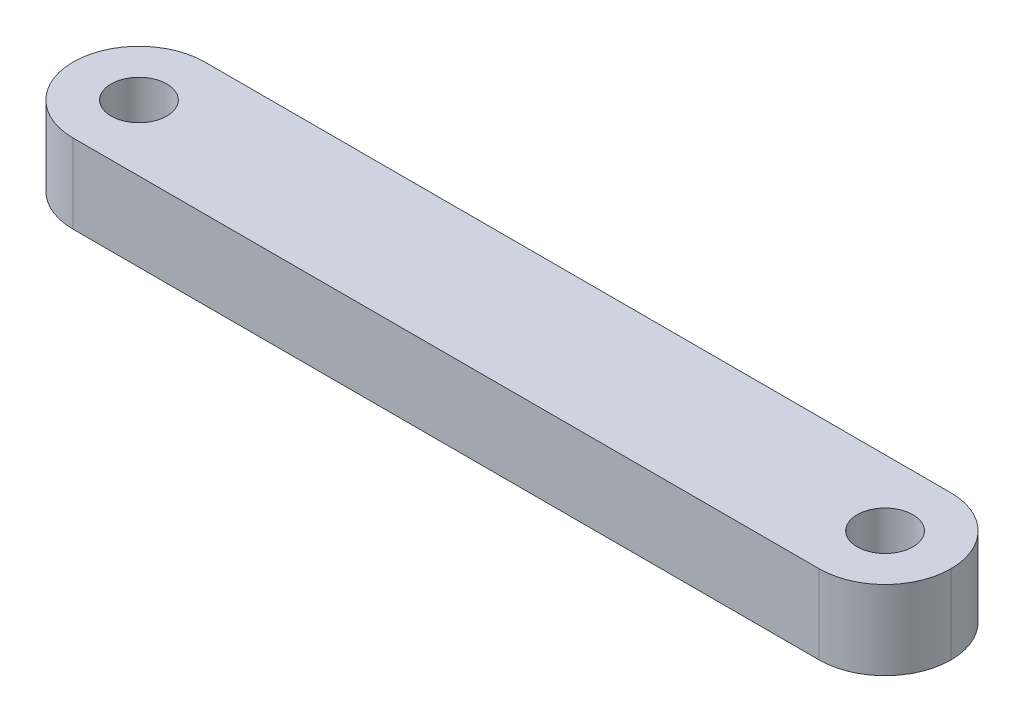
SolidWorks part; units mm, degrees
material "Custom Plastic"
ref_plane "Front Plane" through (0, 0, 0) normal (0, 0, 1) x (1, 0, 0)
ref_plane "Top Plane" through (0, 0, 0) normal (0, 1, 0) x (1, 0, 0)
ref_plane "Right Plane" through (0, 0, 0) normal (1, 0, 0) x (0, 0, -1)
sketch "Sketch1" plane through (0, 0, 0) normal (0, 1, 0) x (1, 0, 0)
  line L0 (-50, -7.5) -> (-42.5, -7.5)
  line L9 (-50, -7.5) -> (50, -7.5)
  line L10 (-50, -7.5) -> (-50, 7.5)
  line L11 (-50, 7.5) -> (50, 7.5)
  line L12 (50, -7.5) -> (50, 7.5)
  line L17 (-50, -7.5) -> (50, 7.5) construction
  line L18 (-50, 7.5) -> (50, -7.5) construction
  line L20 (-42.5, -7.5) -> (-42.5, 7.5)
  line L22 (50, -7.5) -> (42.5, -7.5)
  line L23 (42.5, -7.5) -> (42.5, 7.5)
  circle A0 centre (-42.5, 0) radius 3.175
  circle A1 centre (42.5, 0) radius 3.175
  point P0 (0, 0)
  dimension "D5" = 6.35
  dimension "D1" = 100
  dimension "D2" = 15
  dimension "D4" = 7.5
  dimension "D3" = 7.5
extrude "Boss-Extrude1" add sketch "Sketch1" along normal blind 9 contours A0 L20 L11 L10 L0 | A1 L23 L11 L20 A0 L9 | A1 L23 L9 L12 L11 region at (-46.6435, 0, 0) region at (0, 0, 0) region at (46.6435, 0, 0)
fillet "Fillet1" radius 7.5 4 edges at (50, 4.5, 7.5) (50, 4.5, -7.5) (-50, 4.5, 7.5) (-50, 4.5, -7.5)
